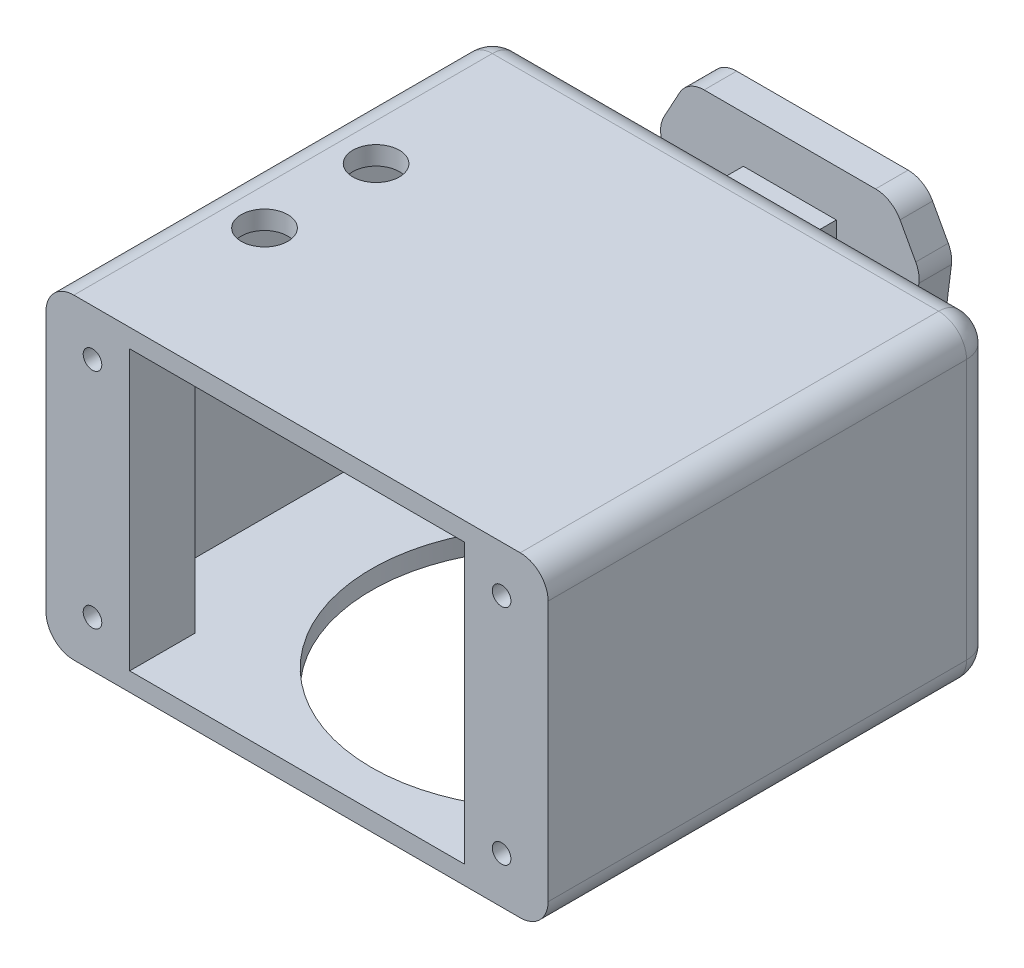
SolidWorks part; units mm, degrees
ref_plane "Front Plane" through (0, 0, 0) normal (0, 0, 1) x (1, 0, 0)
ref_plane "Top Plane" through (0, 0, 0) normal (0, 1, 0) x (1, 0, 0)
ref_plane "Right Plane" through (0, 0, 0) normal (1, 0, 0) x (0, 0, -1)
sketch "Sketch1" plane through (0, 0, 0) normal (0, 0, 1) x (1, 0, 0)
  line L0 (3, 34.1925) -> (3, -19.8735) construction
  line L1 (0, 0) -> (28, 0)
  line L2 (0, 0) -> (0, 29.5)
  line L3 (0, 29.5) -> (28, 29.5)
  line L4 (28, 0) -> (28, 29.5)
  line L5 (25, 34.1925) -> (25, -23.954) construction
  line L6 (-24.9685, 24) -> (62.4766, 24) construction
  line L7 (3, 29.5) -> (0, 24)
  line L8 (25, 29.5) -> (28, 24)
  line L9 (0, 24) -> (3, 0)
  line L10 (28, 24) -> (25, 0)
  dimension "D1" = 29.5
  dimension "D2" = 28
  dimension "D3" = 3
  dimension "D4" = 3
  dimension "D5" = 24
  dimension "D6" = 61.39
extrude "Boss-Extrude1" add sketch "Sketch1" against normal blind 3.5 contours L10 L8 L3 L7 L9 L1 region at (14, 15.12, 0)
sketch "Sketch2" plane through (0, 0, 0) normal (0, 0, 1) x (1, 0, 0)
  line L0 (3, 29.5) -> (25, 29.5) construction
  line L1 (9, 19.5) -> (19, 19.5)
  line L2 (9, 19.5) -> (9, 16.5)
  line L3 (9, 16.5) -> (19, 16.5)
  line L4 (19, 19.5) -> (19, 16.5)
  dimension "D1" = 10
  dimension "D2" = 10
  dimension "D3" = 9
  dimension "D4" = 3
extrude "Boss-Extrude2" add sketch "Sketch2" along normal blind 5 contours L2 L1 L4 L3
ref_plane "Plane1" through (0, 0, 5) normal (0, 0, 1) x (1, 0, 0)
sketch "Sketch3" plane through (0, 0, 5) normal (0, 0, 1) x (1, 0, 0)
  line L0 (9, 19.5) -> (9, 16.5) construction
  line L1 (-11, 29.5) -> (39, 29.5)
  line L2 (-11, 29.5) -> (-11, 5.5)
  line L3 (-11, 5.5) -> (39, 5.5)
  line L4 (39, 29.5) -> (39, 5.5)
  line L5 (9, 19.5) -> (19, 19.5) construction
  dimension "D1" = 50
  dimension "D2" = 20
  dimension "D3" = 10
  dimension "D4" = 24
extrude "Boss-Extrude3" add sketch "Sketch3" along normal blind 3
sketch "Sketch4" plane through (0, 0, 8) normal (0, 0, 1) x (1, 0, 0)
  line L0 (39, 5.5) -> (39, 29.5) construction
  line L1 (-11, 29.5) -> (39, 29.5)
  line L2 (-11, 29.5) -> (-11, 26.5)
  line L3 (-11, 26.5) -> (39, 26.5)
  line L4 (39, 29.5) -> (39, 26.5)
  dimension "D1" = 3
extrude "Boss-Extrude4" add sketch "Sketch4" along normal blind 35 contours L2 L1 L4 L3
sketch "Sketch5" plane through (0, 29.5, 0) normal (0, 1, 0) x (1, 0, 0)
  line L0 (39, -43) -> (39, -5) construction
  line L1 (-8, -40) -> (-4, -40)
  line L2 (-8, -40) -> (-8, -11)
  line L3 (-8, -11) -> (-4, -11)
  line L4 (-4, -40) -> (-4, -11)
  line L5 (-11, -43) -> (39, -43) construction
  point P6 (-6, -40)
  dimension "D1" = 43
  dimension "D2" = 29
  dimension "D3" = 4
  dimension "D4" = 3
extrude "Cut-Extrude3" cut sketch "Sketch5" against normal blind 35
fillet "Fillet1" radius 2 4 edges at (-8, 28, 40) (-4, 28, 40) (-4, 28, 11) (-8, 28, 11)
ref_plane "Plane2" through (39, 0, 0) normal (1, 0, 0) x (0, 0, -1)
sketch "Sketch6" plane through (39, 0, 0) normal (1, 0, 0) x (0, 0, -1)
  line L0 (-25.5, 7.4735) -> (-25.5, 42.9501) construction
  line L1 (-43, 29.5) -> (-43, 26.5) construction
  line L2 (-43, 29.5) -> (-43, 26.5) construction
  line L3 (-43, 29.5) -> (-5, 29.5) construction
  line L4 (-31, 39.5886) -> (-31, 23.7367) construction
  line L5 (-20, 39.0568) -> (-20, 23.7367) construction
  line L6 (-8, 5.5) -> (-8, 26.5) construction
  line L7 (-35.6143, 38.5) -> (-11.4464, 38.5) construction
  line L8 (-43, 29.5) -> (-29.2749, 38.5)
  line L9 (-5, 29.5) -> (-21.7251, 38.5)
  line L10 (-43, 29.5) -> (-5, 29.5)
  circle A0 centre (-25.5, 34.5) radius 3.175
  circle A1 centre (-25.5, 34.5) radius 5.5
  dimension "D2" = 6.35
  dimension "D1" = 17.5
  dimension "D3" = 5
  dimension "D4" = 12
  dimension "D5" = 12
  dimension "D6" = 9
  dimension "D7" = 28.285
extrude "Boss-Extrude6" add sketch "Sketch6" against normal blind 35 contours A1 L8 L10 | A1 L10 A0 | A1 L10 L9 region at (39, 32.1062, 34.4862) region at (39, 39.8479, 25.5) region at (39, 32.1863, 15.5094)
fillet "Fillet2" radius 3 6 edges at (3, 0, -1.75) (25, 0, -1.75) (3, 29.5, -1.75) (25, 29.5, -1.75) (0, 24, -1.75) (28, 24, -1.75)
sketch "Sketch8" plane through (0, 19.5, 0) normal (0, 1, 0) x (1, 0, 0)
  line L1 (19, -5) -> (9, -5)
  line L2 (19, -5) -> (19, 0)
  line L3 (19, 0) -> (9, 0)
  line L4 (9, -5) -> (9, 0)
extrude "Boss-Extrude7" add sketch "Sketch8" along normal blind 10
sketch "Sketch9" plane through (0, 16.5, 0) normal (0, -1, 0) x (1, 0, 0)
  line L1 (9, 5) -> (19, 5)
  line L2 (9, 5) -> (9, 0)
  line L3 (9, 0) -> (19, 0)
  line L4 (19, 5) -> (19, 0)
extrude "Boss-Extrude8" add sketch "Sketch9" along normal blind 10
sketch "Sketch10" plane through (0, 29.5, 0) normal (0, 1, 0) x (1, 0, 0)
  line L1 (4, -5) -> (57.5143, -5)
  line L2 (4, -5) -> (4, -47.4892)
  line L3 (4, -47.4892) -> (57.5143, -47.4892)
  line L4 (57.5143, -5) -> (57.5143, -47.4892)
  dimension "D1" = 53.5143
  dimension "D2" = 42.4892
extrude "Cut-Extrude4" cut sketch "Sketch10" along normal blind 20
sketch "Sketch11" plane through (39, 0, 0) normal (1, 0, 0) x (0, 0, -1)
  line L0 (-5, 16.225) -> (-5, -16.225) construction
  line L1 (-43, 29.5) -> (-5, 29.5)
  line L2 (-43, 29.5) -> (-43, 39.5)
  line L3 (-43, 39.5) -> (-5, 39.5)
  line L4 (-5, 29.5) -> (-5, 39.5)
  line L5 (-24, 39.5) -> (-24, 29.5) construction
  circle A0 centre (-24, 39.5) radius 5
  dimension "D3" = 10
  dimension "D1" = 0
  dimension "D2" = 10
extrude "Boss-Extrude9" add sketch "Sketch11" against normal blind 40 contours L5 A0 L3 L2 L1 | A0 L5 L1 L4 L3 region at (39, 34.1683, 34.3503) region at (39, 34.1683, 13.6497)
sketch "Sketch12" plane through (0, 0, 43) normal (0, 0, 1) x (1, 0, 0)
sketch "Sketch13" plane through (0, 0, 43) normal (0, 0, 1) x (1, 0, 0)
  line L0 (-11, 26.5) -> (39, 26.5) construction
  line L1 (-11, 29.5) -> (39, 29.5)
  line L2 (-11, 29.5) -> (-11, 26.5)
  line L3 (-11, 26.5) -> (39, 26.5)
  line L4 (39, 29.5) -> (39, 26.5)
  line L5 (39, 39.5) -> (39, 26.5) construction
  line L7 (-1, 39.5) -> (39, 39.5)
  line L8 (-1, 39.5) -> (-1, 29.5)
  line L9 (-1, 29.5) -> (39, 29.5)
  line L10 (39, 39.5) -> (39, 29.5)
  line M1 (-11, 26.5) -> (39, 26.5)
  line M2 (39, 26.5) -> (39, 39.5)
  line M3 (39, 39.5) -> (-1, 39.5)
  line M4 (-1, 39.5) -> (-1, 29.5)
  line M5 (-1, 29.5) -> (-11, 29.5)
  line M6 (-11, 29.5) -> (-11, 26.5)
extrude "Boss-Extrude10" add sketch "Sketch13" along normal blind 20 contours L1 M4 M2 M3 | L1 M5 M6 M1 M2 region at (14, 28, 43) region at (19, 34.5, 43)
sketch "Sketch14" plane through (0, 29.5, 0) normal (0, 1, 0) x (1, 0, 0)
  line L0 (-8, -13) -> (-8, -38) construction
  line L1 (-4, -38) -> (-8, -38)
  line L2 (-4, -38) -> (-4, -58)
  line L3 (-4, -58) -> (-8, -58)
  line L4 (-8, -38) -> (-8, -58)
  line L5 (-1, -63) -> (-1, -5) construction
  arc A0 (-6, -40) -> (-4, -38) centre (-6, -38) ccw construction
  dimension "D1" = 0
  dimension "D2" = 20
  dimension "D3" = 3
extrude "Cut-Extrude7" cut sketch "Sketch14" against normal blind 20
fillet "Fillet3" radius 2 2 edges at (-8, 28, 58) (-4, 28, 58)
sketch "Sketch16" plane through (0, 0, 5) normal (0, 0, -1) x (-1, 0, 0)
  line L0 (-39, 5.5) -> (-39, 39.5) construction
  line L1 (1, 39.5) -> (-39, 39.5)
  line L2 (1, 39.5) -> (1, 29.5)
  line L3 (1, 29.5) -> (-39, 29.5)
  line L4 (-39, 39.5) -> (-39, 29.5)
  dimension "D1" = 10
extrude "Cut-Extrude9" cut sketch "Sketch16" against normal blind 4
sketch "Sketch19" plane through (0, 0, 63) normal (0, 0, 1) x (1, 0, 0)
  line L0 (39, 26.5) -> (39, 39.5) construction
  line L1 (-1, 39.5) -> (39, 39.5)
  line L2 (-1, 39.5) -> (-1, 29.5)
  line L3 (-1, 29.5) -> (39, 29.5)
  line L4 (39, 39.5) -> (39, 29.5)
  dimension "D1" = 10
extrude "Cut-Extrude10" cut sketch "Sketch19" against normal blind 24
sketch "Sketch20" plane through (0, 0, 39) normal (0, 0, 1) x (1, 0, 0)
  line L0 (-1, 29.5) -> (39, 29.5) construction
  line L1 (4, 32.5) -> (8, 32.5)
  line L2 (4, 32.5) -> (4, 30.5)
  line L3 (4, 30.5) -> (8, 30.5)
  line L4 (8, 32.5) -> (8, 30.5)
  line L5 (30, 32.5) -> (34, 32.5)
  line L6 (30, 32.5) -> (30, 30.5)
  line L7 (30, 30.5) -> (34, 30.5)
  line L8 (34, 32.5) -> (34, 30.5)
  line L9 (-1, 39.5) -> (-1, 29.5) construction
  line L10 (39, 29.5) -> (39, 39.5) construction
  point P10 (8, 31.5)
  dimension "D1" = 1
  dimension "D2" = 1
  dimension "D3" = 4
  dimension "D4" = 4
  dimension "D5" = 2
  dimension "D6" = 2
  dimension "D7" = 5
  dimension "D8" = 5
extrude "Cut-Extrude11" cut sketch "Sketch20" against normal blind 44
fillet "Fillet4" radius 10 2 edges at (19, 39.5, 9) (19, 39.5, 39)
sketch "Sketch21" plane through (-11, 0, 0) normal (-1, 0, 0) x (0, 0, 1)
  line L1 (63, 29.5) -> (5, 29.5)
  line L2 (63, 29.5) -> (63, 5.5)
  line L3 (63, 5.5) -> (5, 5.5)
  line L4 (5, 29.5) -> (5, 5.5)
extrude "Boss-Extrude11" add sketch "Sketch21" along normal blind 2
ref_plane "Plane3" through (0, 0, 65) normal (0, 0, 1) x (1, 0, 0)
sketch "Sketch22" plane through (0, 0, 65) normal (0, 0, 1) x (1, 0, 0)
  line L0 (-13, 29.5) -> (39, 29.5) construction
  line L1 (-13.5647, 41.5) -> (40.746, 41.5)
  line L2 (-13.5647, 41.5) -> (-13.5647, 1.5)
  line L3 (-13.5647, 1.5) -> (40.746, 1.5)
  line L4 (40.746, 41.5) -> (40.746, 1.5)
  line L5 (-13, 5.5) -> (-13, 29.5) construction
  dimension "D1" = 54.3107
  dimension "D2" = 40
  dimension "D3" = 12
  dimension "D4" = 0.5647
extrude "Cut-Extrude14" cut sketch "Sketch22" against normal up to surface (57 mm away) up to face at (14, 16, 8)
sketch "Sketch24" plane through (0, 29.5, 0) normal (0, 1, 0) x (1, 0, 0)
  line L1 (9, 0) -> (19, 0)
  line L2 (9, 0) -> (9, -5)
  line L3 (9, -5) -> (19, -5)
  line L4 (19, 0) -> (19, -5)
extrude "Cut-Extrude15" cut sketch "Sketch24" against normal blind 5
sketch "Sketch25" plane through (0, 0, 8) normal (0, 0, 1) x (1, 0, 0)
  line L0 (39, 29.5) -> (-13, 29.5) construction
  line L1 (-13, 29.5) -> (39, 29.5)
  line L2 (-13, 29.5) -> (-13, 27.5)
  line L3 (-13, 27.5) -> (39, 27.5)
  line L4 (39, 29.5) -> (39, 27.5)
  line L5 (-13, 29.5) -> (-13, 5.5) construction
  line L6 (39, -1.65) -> (39, 1.65) construction
  dimension "D1" = 0
  dimension "D2" = 0
  dimension "D3" = 2
  dimension "D4" = 0
extrude "Boss-Extrude12" add sketch "Sketch25" along normal blind 45
sketch "Sketch26" plane through (0, 27.5, 0) normal (0, -1, 0) x (1, 0, 0)
  line L0 (-13, 8) -> (39, 8) construction
  line L1 (-13, 53) -> (-11, 53)
  line L2 (-13, 53) -> (-13, 8)
  line L3 (-13, 8) -> (-11, 8)
  line L4 (-11, 53) -> (-11, 8)
  dimension "D1" = 0
  dimension "D2" = 2
extrude "Boss-Extrude13" add sketch "Sketch26" along normal up to surface (22 mm away) up to face at (13, 5.5, 6.5)
sketch "Sketch27" plane through (0, 27.5, 0) normal (0, -1, 0) x (1, 0, 0)
  line L0 (-34.9799, 30.5) -> (56.2428, 30.5) construction
  line L3 (-11, 53) -> (39, 53) construction
  line L5 (-6, 50.1466) -> (-6, 11.1277) construction
  line L6 (-11, 8) -> (-11, 53) construction
  line L7 (-3.1371, 36.5) -> (-9.2513, 36.5) construction
  line L8 (-3.1371, 24.5) -> (-9.2513, 24.5) construction
  circle A0 centre (-6, 36.5) radius 2.5
  circle A1 centre (-6, 24.5) radius 2.5
  dimension "D5" = 5
  dimension "D6" = 5
  dimension "D1" = 22.5
  dimension "D2" = 5
  dimension "D3" = 6
  dimension "D4" = 6
extrude "Cut-Extrude16" cut sketch "Sketch27" against normal blind 45
sketch "Sketch28" plane through (0, 5.5, 0) normal (0, -1, 0) x (1, 0, 0)
sketch "Sketch29" plane through (0, 5.5, 0) normal (0, -1, 0) x (1, 0, 0)
  line L1 (-13, 53) -> (-11, 53)
  line L2 (-13, 53) -> (-13, 8)
  line L3 (-13, 8) -> (-11, 8)
  line L4 (-11, 53) -> (-11, 8)
  line L5 (-13, 5) -> (39, 5)
  line L6 (-13, 5) -> (-13, 8)
  line L7 (-13, 8) -> (39, 8)
  line L8 (39, 5) -> (39, 8)
  line M5 (39, 8) -> (-11, 8)
  line M6 (-11, 8) -> (-11, 53)
  line M7 (-11, 53) -> (-13, 53)
  line M8 (-13, 53) -> (-13, 5)
  line M9 (-13, 5) -> (39, 5)
  line M10 (39, 5) -> (39, 8)
extrude "Boss-Extrude14" add sketch "Sketch29" along normal blind 10 contours L3 M8 M6 M7 | L3 M8 M9 M10 M5 region at (-12, 5.5, 30.5) region at (13, 5.5, 6.5)
sketch "Sketch30" plane through (-11, 0, 0) normal (1, 0, 0) x (0, 0, -1)
  line L0 (-8, -4.5) -> (-53, -4.5) construction
  line L1 (-53, -2.5) -> (-8, -2.5)
  line L2 (-53, -2.5) -> (-53, -4.5)
  line L3 (-53, -4.5) -> (-8, -4.5)
  line L4 (-8, -2.5) -> (-8, -4.5)
  line L5 (-53, -4.5) -> (-53, 27.5) construction
  line L6 (-8, -4.5) -> (-8, 27.5) construction
  dimension "D1" = 0
  dimension "D2" = 0
  dimension "D3" = 0
  dimension "D4" = 2
extrude "Boss-Extrude15" add sketch "Sketch30" along normal up to surface (50 mm away) up to face at (39, 17.5, 22)
sketch "Sketch31" plane through (0, 27.5, 0) normal (0, -1, 0) x (1, 0, 0)
  line L0 (18, 46.7775) -> (18, 25.6971) construction
  line L2 (13.1309, 30.5) -> (37.427, 30.5) construction
  circle A0 centre (-6, 36.5) radius 2.5 construction
  circle A2 centre (18, 30.5) radius 18.5
  dimension "D3" = 37
  dimension "D1" = 24
  dimension "D2" = 6
extrude "Cut-Extrude17" cut sketch "Sketch31" along normal blind 60
sketch "Sketch32" plane through (39, 0, 0) normal (1, 0, 0) x (0, 0, -1)
  line L0 (-5, -4.5) -> (-53, -4.5) construction
  line L1 (-5, 29.5) -> (-8, 29.5)
  line L2 (-5, 29.5) -> (-5, -4.5)
  line L3 (-5, -4.5) -> (-8, -4.5)
  line L4 (-8, 29.5) -> (-8, -4.5)
  line L5 (-8, -2.5) -> (-8, 27.5) construction
  dimension "D1" = 0
extrude "Boss-Extrude17" add sketch "Sketch32" along normal blind 2
sketch "Sketch33" plane through (0, 0, 8) normal (0, 0, 1) x (1, 0, 0)
  line L1 (41, 29.5) -> (39, 29.5)
  line L2 (41, 29.5) -> (41, -4.5)
  line L3 (41, -4.5) -> (39, -4.5)
  line L4 (39, 29.5) -> (39, -4.5)
extrude "Boss-Extrude18" add sketch "Sketch33" along normal up to surface (45 mm away) up to face at (13.5, 12.5, 53)
sketch "Sketch37" plane through (0, -2.5, 0) normal (0, 1, 0) x (1, 0, 0)
  line L0 (-11, -8) -> (-11, -53) construction
  line L1 (-11, -46) -> (-4, -46)
  line L2 (-11, -46) -> (-11, -53)
  line L3 (-11, -53) -> (-4, -53)
  line L4 (-4, -46) -> (-4, -53)
  line L5 (39, -53) -> (-11, -53) construction
  line L6 (39, -53) -> (39, -8) construction
  line L7 (39, -46) -> (32, -46)
  line L8 (39, -46) -> (39, -53)
  line L9 (39, -53) -> (32, -53)
  line L10 (32, -46) -> (32, -53)
  dimension "D1" = 7
  dimension "D2" = 7
  dimension "D3" = 7
  dimension "D4" = 7
extrude "Boss-Extrude20" add sketch "Sketch37" along normal up to next
sketch "Sketch38" plane through (0, 0, 53) normal (0, 0, 1) x (1, 0, 0)
  line L0 (-8, 28.4022) -> (-8, -3.1315) construction
  line L1 (36, 27.8149) -> (36, -3.1315) construction
  line L2 (-13, 29.5) -> (-13, -4.5) construction
  line L3 (41, -4.5) -> (41, 29.5) construction
  line L4 (-20.7656, 24.5) -> (46.9546, 24.5) construction
  line L5 (-22.516, 0.5) -> (46.517, 0.5) construction
  line L6 (41, -4.5) -> (-13, -4.5) construction
  line L7 (41, 29.5) -> (-13, 29.5) construction
  circle A0 centre (-8, 24.5) radius 1
  circle A1 centre (-8, 0.5) radius 1
  circle A2 centre (36, 24.5) radius 1
  circle A3 centre (36, 0.5) radius 1
  dimension "D5" = 2
  dimension "D6" = 2
  dimension "D7" = 2
  dimension "D8" = 2
  dimension "D1" = 5
  dimension "D2" = 5
  dimension "D3" = 5
  dimension "D4" = 5
extrude "Cut-Extrude18" cut sketch "Sketch38" against normal blind 16
fillet "Fillet5" radius 3 4 edges at (-13, -4.5, 29) (-13, 29.5, 29) (41, -4.5, 29) (41, 29.5, 29)
fillet "Fillet6" radius 3 8 edges at (40.1213, 28.6213, 5) (41, 12.5, 5) (40.1213, -3.6213, 5) (14, -4.5, 5) (-12.1213, -3.6213, 5) (-13, 12.5, 5) (-12.1213, 28.6213, 5) (14, 29.5, 5)
sketch "Sketch39" plane through (-13, 0, 0) normal (-1, 0, 0) x (0, 0, 1)
  line L0 (8, 26.5) -> (8, -1.5) construction
  line L1 (10, 15.5) -> (15, 15.5)
  line L2 (10, 15.5) -> (10, 10.5)
  line L3 (10, 10.5) -> (15, 10.5)
  line L4 (15, 15.5) -> (15, 10.5)
  line L5 (8, -1.5) -> (53, -1.5) construction
  dimension "D1" = 5
  dimension "D2" = 5
  dimension "D3" = 2
  dimension "D4" = 12
extrude "Cut-Extrude22" cut sketch "Sketch39" against normal blind 10
fillet "Fillet7" radius 1 4 edges at (-12, 10.5, 15) (-12, 10.5, 10) (-12, 15.5, 15) (-12, 15.5, 10)
ref_plane "Plane6" through (0, 0, 46) normal (0, 0, 1) x (1, 0, 0)
sketch "Sketch40" plane through (0, 0, 46) normal (0, 0, 1) x (1, 0, 0)
  line L1 (-4, 27.5) -> (-11, 27.5)
  line L2 (-4, 27.5) -> (-4, -2.5)
  line L3 (-4, -2.5) -> (-11, -2.5)
  line L4 (-11, 27.5) -> (-11, -2.5)
  line L5 (32, 27.5) -> (39, 27.5)
  line L6 (32, 27.5) -> (32, -2.5)
  line L7 (32, -2.5) -> (39, -2.5)
  line L8 (39, 27.5) -> (39, -2.5)
  dimension "D1" = 7
  dimension "D2" = 30
  dimension "D3" = 30
  dimension "D4" = 7
extrude "Boss-Extrude21" add sketch "Sketch40" along normal blind 0.2
